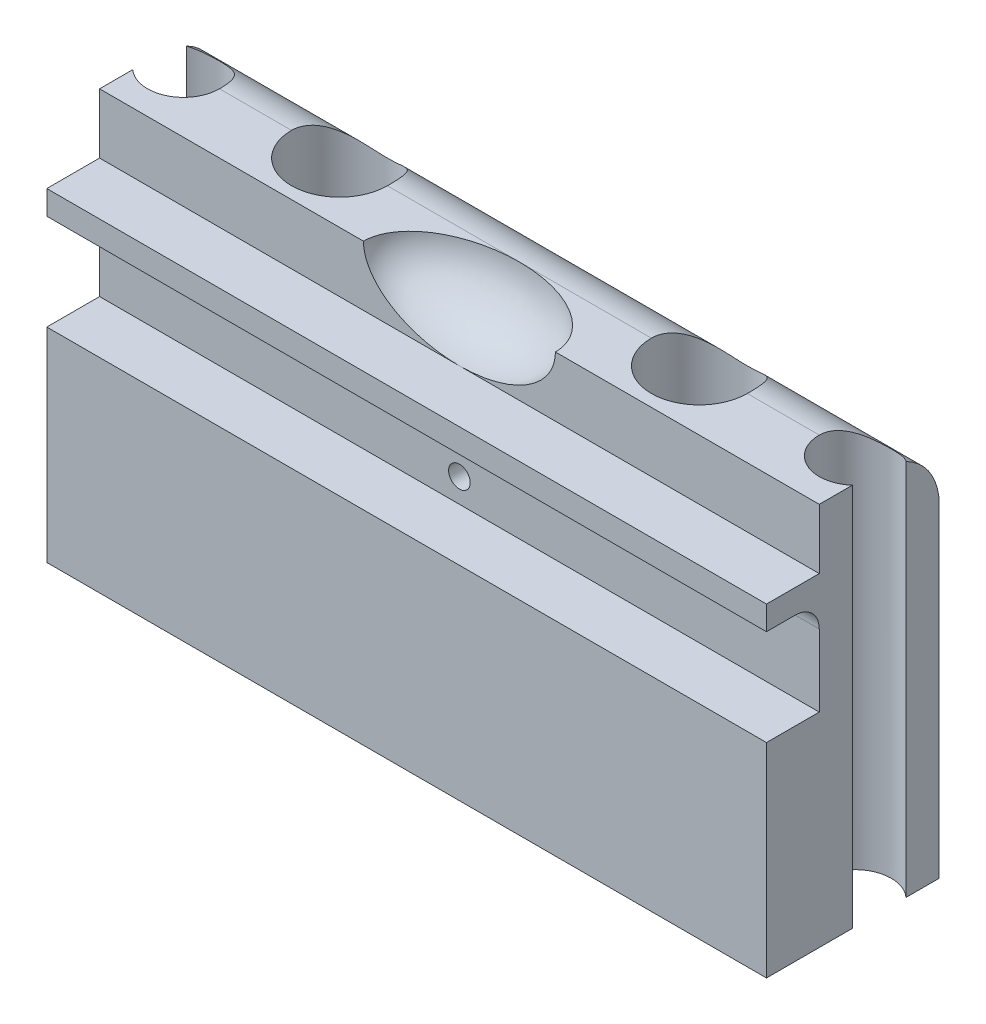
SolidWorks part; units mm, degrees
ref_plane "Front Plane" through (0, 0, 0) normal (0, 0, 1) x (1, 0, 0)
ref_plane "Top Plane" through (0, 0, 0) normal (0, 1, 0) x (1, 0, 0)
ref_plane "Right Plane" through (0, 0, 0) normal (1, 0, 0) x (0, 0, -1)
sketch "Sketch2" plane through (0, 0, 0) normal (1, 0, 0) x (0, 0, -1)
  line L1 (0, 0) -> (18.288, 0)
  line L2 (0, 0) -> (0, 40.64)
  line L3 (0, 40.64) -> (18.288, 40.64)
  line L4 (18.288, 0) -> (18.288, 40.64)
  dimension "D1" = 18.288
  dimension "D2" = 40.64
extrude "Boss-Extrude1" add sketch "Sketch2" along normal blind 76.2
sketch "Sketch3" plane through (0, 0, 0) normal (-1, 0, 0) x (0, 0, 1)
  line L0 (-18.288, 0) -> (-18.288, 40.64) construction
  line L1 (0, 40.64) -> (-5.588, 40.64)
  line L2 (0, 40.64) -> (0, 34.29)
  line L3 (0, 34.29) -> (-5.588, 34.29)
  line L4 (-5.588, 40.64) -> (-5.588, 34.29)
  line L5 (0, 40.64) -> (0, 0) construction
  line L6 (0, 31.75) -> (-5.588, 31.75)
  line L7 (0, 31.75) -> (0, 21.59)
  line L8 (0, 21.59) -> (-5.588, 21.59)
  line L9 (-5.588, 31.75) -> (-5.588, 21.59)
  dimension "D1" = 6.35
  dimension "D2" = 12.7
  dimension "D3" = 2.54
  dimension "D4" = 10.16
  dimension "D5" = 12.7
extrude "Cut-Extrude1" cut sketch "Sketch3" against normal up to next
sketch "Sketch4" plane through (0, 0, -5.588) normal (0, 0, 1) x (1, 0, 0)
  line L0 (0, 31.75) -> (0, 21.59) construction
  line L1 (76.2, 21.59) -> (0, 21.59) construction
  circle A0 centre (38.1, 24.13) radius 1.143
  point P2 (0, 0)
  dimension "D1" = 2.286
  dimension "D2" = 38.1
  dimension "D3" = 2.54
extrude "Cut-Extrude2" cut sketch "Sketch4" against normal up to next
sketch "Sketch5" plane through (0, 40.64, 0) normal (0, 1, 0) x (1, 0, 0)
  line L0 (38.1, 18.288) -> (38.1, 5.588) construction
  line L1 (76.2, 18.288) -> (0, 18.288) construction
  line L2 (76.2, 5.588) -> (0, 5.588) construction
  line L3 (76.2, 11.938) -> (0, 11.938) construction
  line L4 (76.2, 18.288) -> (76.2, 5.588) construction
  line L5 (0, 18.288) -> (0, 5.588) construction
  circle A0 centre (57.15, 11.938) radius 2.032
  circle A1 centre (19.05, 11.938) radius 2.032
  dimension "D1" = 4.064
  dimension "D2" = 4.064
  dimension "D3" = 19.05
  dimension "D4" = 19.05
extrude "Cut-Extrude3" cut sketch "Sketch5" against normal up to next
sketch "Sketch6" plane through (0, 40.64, 0) normal (0, 1, 0) x (1, 0, 0)
  circle A0 centre (19.05, 11.938) radius 5.08
  circle A1 centre (57.15, 11.938) radius 5.08
  dimension "D1" = 10.16
  dimension "D2" = 10.16
extrude "Cut-Extrude4" cut sketch "Sketch6" against normal offset from surface (15.24 mm away) 25.4 up to face at (57.15, 0, -9.906)
fillet "Fillet1" radius 6.35 1 edges at (38.1, 40.64, -18.288)
fillet "Fillet2" radius 2.54 1 edges at (38.1, 31.75, -5.588)
sketch "Sketch7" plane through (0, 0, 0) normal (0, -1, 0) x (1, 0, 0)
  line L0 (0, -11.938) -> (76.2, -11.938) construction
  line L1 (0, 0) -> (0, -18.288) construction
  line L2 (76.2, 0) -> (76.2, -18.288) construction
  line L3 (76.2, -18.288) -> (0, -18.288) construction
  circle A0 centre (2.54, -11.938) radius 3.81
  circle A1 centre (73.66, -11.938) radius 3.81
  dimension "D3" = 7.62
  dimension "D4" = 7.62
  dimension "D1" = 6.35
  dimension "D2" = 2.54
  dimension "D5" = 2.54
extrude "Cut-Extrude5" cut sketch "Sketch7" against normal through all
sketch "Sketch8" plane through (0, 0, -5.588) normal (0, 0, 1) x (1, 0, 0)
  line L0 (38.1, 40.64) -> (38.1, 34.29) construction
  line L1 (76.2, 40.64) -> (0, 40.64) construction
  line L2 (76.2, 34.29) -> (0, 34.29) construction
  line L3 (27.94, 40.64) -> (48.26, 40.64) construction
  line L4 (27.94, 40.64) -> (48.26, 40.64)
  ellipse E0 centre (38.1, 40.64) end of major axis (27.94, 40.64) minor radius 6.35 (27.94, 40.64) -> (48.26, 40.64) ccw
  point P6 (0, 0)
  dimension "D1" = 20.32
revolve "Cut-Revolve3" cut sketch "Sketch8" angle 360 about axis through (76.201, 40.64, -5.588) along (-1, 0, 0) reverse direction yes
